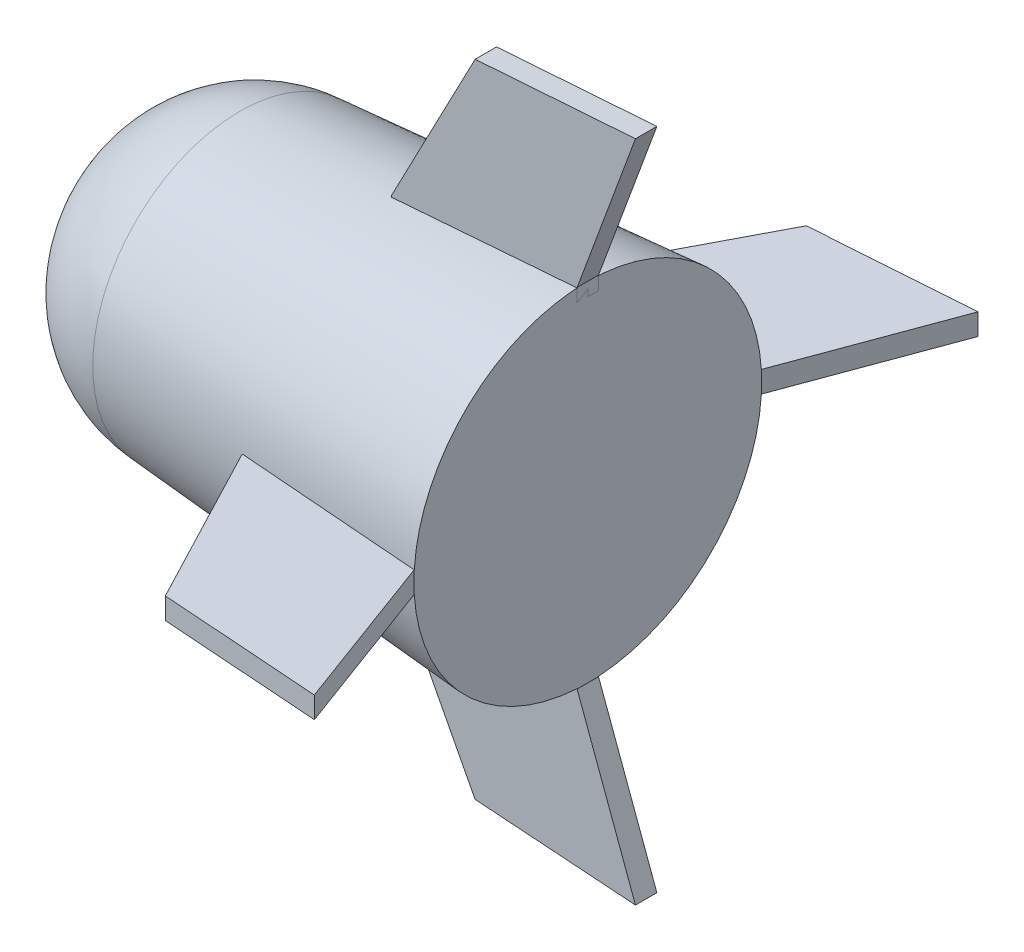
SolidWorks part; units mm, degrees
ref_plane "Front Plane" through (0, 0, 0) normal (0, 0, 1) x (1, 0, 0)
ref_plane "Top Plane" through (0, 0, 0) normal (0, 1, 0) x (1, 0, 0)
ref_plane "Right Plane" through (0, 0, 0) normal (1, 0, 0) x (0, 0, -1)
sketch "Sketch1" plane through (0, 0, 0) normal (0, 0, 1) x (1, 0, 0)
  line L1 (130, 0) -> (130, 65)
  line L2 (130, 65) -> (-0.0882, 54.9932)
  line L5 (-47.3077, -0.0001) -> (130, 0)
  arc A0 (-0.0882, 54.9932) -> (-47.3077, -0.0001) centre (3.8462, 3.8461) ccw
  dimension "D2" = 65
revolve "Revolve2" add sketch "Sketch1" angle 360 about L5
ref_plane "Plane1" through (0, 60, 0) normal (0, 1, 0) x (1, 0, 0)
sketch "Sketch3" plane through (0, 60, 0) normal (0, 1, 0) x (1, 0, 0)
  line L0 (70.2956, 0) -> (121.2694, 0)
  line L1 (121.2694, -4.3718) -> (121.2694, 4.3718)
  line L2 (121.2694, 4.3718) -> (70.2956, 4.3718)
  line L3 (70.2956, 4.3718) -> (70.2956, -4.3718)
  line L4 (70.2956, 0) -> (121.2694, 0)
  line L5 (121.2694, -4.3718) -> (70.2956, -4.3718)
sketch "Sketch4" plane through (0, 0, 0) normal (0, 0, 1) x (1, 0, 0)
  line L0 (60.567, 60) -> (85.2126, 107.0796)
  line L1 (70.2956, 60) -> (121.2694, 60) construction
  line L2 (70.2956, 60) -> (121.2694, 60) construction
  line L3 (85.2126, 107.0796) -> (91.8789, 119.814)
  line L4 (91.8789, 119.814) -> (151.8109, 124.0432)
  line L5 (151.8109, 124.0432) -> (130, 65)
  line L6 (71.5, 60) -> (-71.5, 60) construction
  line L7 (60.567, 60) -> (60.567, 59.659)
  line L8 (130, 65) -> (-0.0882, 54.9932) construction
  line L9 (60.567, 59.659) -> (130, 65)
extrude "Boss-Extrude1" add sketch "Sketch4" along normal blind 4 and the other way blind 4 separate body
sketch "Sketch7" plane through (-4.2059, 54.6765, 0) normal (0.0767, -0.9971, 0) x (0.9971, 0.0767, 0)
  line L0 (64.9642, 4) -> (64.9642, -4)
  line L1 (64.9642, -4) -> (134.6024, -4)
  line L2 (134.6024, -4) -> (134.6024, 4)
  line L3 (134.6024, 4) -> (64.9642, 4)
extrude "Boss-Extrude3" add sketch "Sketch7" along normal blind 5
sketch "Sketch8" plane through (0, 0, 4) normal (0, 0, 1) x (1, 0, 0)
  line L0 (130.3835, 60.0147) -> (130, 59.9852)
  line L1 (130.0001, -65) -> (130, 65) construction
  line L2 (130.3835, 60.0147) -> (60.9505, 54.6737) construction
  line L3 (130, 59.9852) -> (130, 65)
  line L4 (130, 65) -> (130.3835, 60.0147)
extrude "Cut-Extrude1" cut sketch "Sketch8" against normal blind 8
pattern_circular "CirPattern9" count 4 over 360 about axis through (130, 0, 0) along (-1, 0, 0) of "Boss-Extrude1", "Boss-Extrude3", "Cut-Extrude1"
